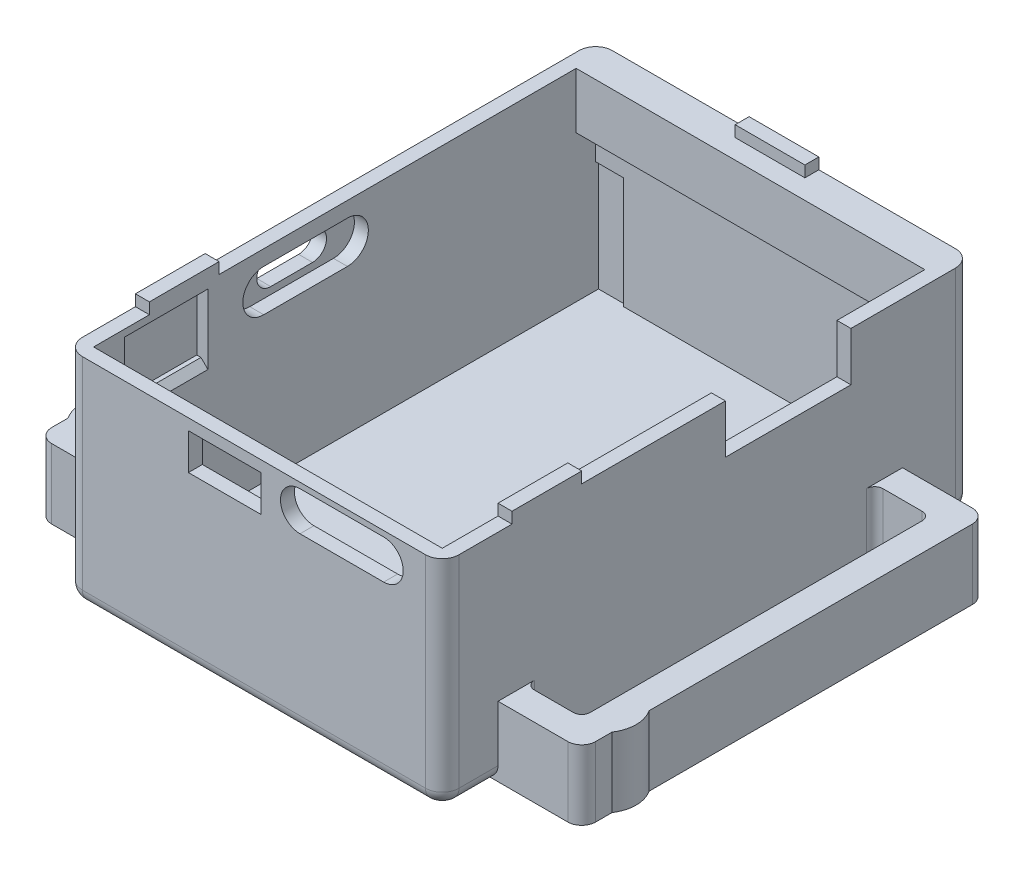
SolidWorks part; units mm, degrees
ref_plane "前视基准面" through (0, 0, 0) normal (0, 0, 1) x (1, 0, 0)
ref_plane "上视基准面" through (0, 0, 0) normal (0, 1, 0) x (1, 0, 0)
ref_plane "右视基准面" through (0, 0, 0) normal (1, 0, 0) x (0, 0, -1)
other "Configuration Table"
sketch "草图1" plane through (0, 0, 0) normal (0, 1, 0) x (1, 0, 0)
  line L1 (-12.5, -18) -> (12.5, -18) construction
  line L2 (-12.5, -18) -> (-12.5, 18) construction
  line L3 (-12.5, 18) -> (12.5, 18) construction
  line L4 (12.5, -18) -> (12.5, 18) construction
  line L5 (-12.5, -18) -> (12.5, 18) construction
  line L6 (-12.5, 18) -> (12.5, -18) construction
  line L7 (-13.5, -19) -> (13.5, -19)
  line L8 (-13.5, -19) -> (-13.5, 19)
  line L9 (-13.5, 19) -> (13.5, 19)
  line L10 (13.5, -19) -> (13.5, 19)
  line L11 (-13.5, -19) -> (13.5, 19) construction
  line L12 (-13.5, 19) -> (13.5, -19) construction
  point P0 (0, 0)
  point P6 (0, 0)
  dimension "D1" = 25
  dimension "D2" = 36
  dimension "D3" = 1
  dimension "D4" = 1
extrude "凸台-拉伸1" add sketch "草图1" along normal blind 1
sketch "草图3" plane through (0, 1, 0) normal (0, 1, 0) x (1, 0, 0)
  line L1 (-13.5, -19) -> (13.5, -19)
  line L2 (-13.5, -19) -> (-13.5, 19)
  line L3 (-13.5, 19) -> (13.5, 19)
  line L4 (13.5, -19) -> (13.5, 19)
  line L5 (-13.5, -19) -> (13.5, 19) construction
  line L6 (-13.5, 19) -> (13.5, -19) construction
  line L7 (-12.5, -18) -> (12.5, -18)
  line L8 (-12.5, -18) -> (-12.5, 18)
  line L9 (-12.5, 18) -> (12.5, 18)
  line L10 (12.5, -18) -> (12.5, 18)
  line L11 (-12.5, -18) -> (12.5, 18) construction
  line L12 (-12.5, 18) -> (12.5, -18) construction
  point P0 (0, 0)
  point P7 (0, 0)
  dimension "D1" = 1
  dimension "D2" = 1
  dimension "D3" = 38
  dimension "D4" = 27
extrude "凸台-拉伸2" add sketch "草图3" along normal blind 14.5
fillet "圆角1" radius 1.2 4 edges at (13.5, 7.75, -19) (-13.5, 7.75, -19) (-13.5, 7.75, 19) (13.5, 7.75, 19)
sketch "草图4" plane through (0, 0, 0) normal (0, -1, 0) x (1, 0, 0)
  line L0 (13.5, 17.8) -> (13.5, -17.8) construction
  line L1 (13.5, 15) -> (19.5, 15)
  line L2 (13.5, 15) -> (13.5, 13)
  line L3 (13.5, -14) -> (19.5, -14)
  line L4 (19.5, 15) -> (19.5, -14)
  line L5 (0, 19) -> (0, -19) construction
  line L6 (13.5, 13) -> (17.5, 13)
  line L8 (13.5, -12) -> (17.5, -12)
  line L9 (17.5, 13) -> (17.5, -12)
  line L10 (-12.3, 19) -> (12.3, 19) construction
  line L11 (12.3, -19) -> (-12.3, -19) construction
  line L12 (-17.5, 13) -> (-17.5, -12)
  line L13 (-13.5, -12) -> (-17.5, -12)
  line L15 (-13.5, 13) -> (-17.5, 13)
  line L16 (-19.5, 15) -> (-19.5, -14)
  line L17 (-13.5, -14) -> (-19.5, -14)
  line L18 (-13.5, 15) -> (-13.5, 13)
  line L19 (-13.5, 15) -> (-19.5, 15)
  line L20 (-13.5, -12) -> (-13.5, -14)
  line L21 (13.5, -12) -> (13.5, -14)
  dimension "D1" = 6
  dimension "D2" = 29
  dimension "D3" = 2
  dimension "D4" = 2
  dimension "D5" = 2
  dimension "D6" = 4
extrude "凸台-拉伸3" add sketch "草图4" against normal blind 5
fillet "圆角3" radius 1 4 edges at (-19.5, 2.5, 15) (-19.5, 2.5, -14) (19.5, 2.5, 15) (19.5, 2.5, -14)
fillet "圆角4" radius 0.6 8 edges at (-17.5, 2.5, 13) (-17.5, 2.5, -12) (-13.5, 2.5, 13) (-13.5, 2.5, -12) (17.5, 2.5, 13) (13.5, 2.5, 13) (13.5, 2.5, -12) (17.5, 2.5, -12)
fillet "圆角6" radius 1 10 edges at (13.5, 0, -15.9) (13.1485, 0, -18.6485) (-13.5, 0, -15.9) (-13.1485, 0, -18.6485) (-13.5, 0, 16.4) (-13.1485, 0, 18.6485) (13.5, 0, 16.4) (13.1485, 0, 18.6485) (0, 0, -19) (0, 0, 19)
sketch "草图5" plane through (0, 0, 19) normal (0, 0, 1) x (1, 0, 0)
  line L0 (3.3, 13.7) -> (9.3, 13.7) construction
  line L1 (3.3, 15.1) -> (9.3, 15.1)
  line L2 (3.3, 12.3) -> (9.3, 12.3)
  line L3 (12.3, 1) -> (12.3, 15.5) construction
  line L4 (-12.3, 15.5) -> (12.3, 15.5) construction
  arc A0 (3.3, 15.1) -> (3.3, 12.3) centre (3.3, 13.7) ccw
  arc A1 (9.3, 12.3) -> (9.3, 15.1) centre (9.3, 13.7) ccw
  point P2 (6.3, 13.7)
  dimension "D2" = 6
  dimension "D3" = 1.4
  dimension "D1" = 6
  dimension "D4" = 0.4
extrude "切除-拉伸1" cut sketch "草图5" against normal up to next
sketch "草图6" plane through (13.5, 0, 0) normal (1, 0, 0) x (0, 0, -1)
  line L0 (-17.8, 15.5) -> (17.8, 15.5) construction
  line L1 (1.3, 15.5) -> (10.3, 15.5)
  line L2 (1.3, 15.5) -> (1.3, 12)
  line L3 (1.3, 12) -> (10.3, 12)
  line L4 (10.3, 15.5) -> (10.3, 12)
  line L6 (-19, 1) -> (-19, 15.5) construction
  dimension "D1" = 3.5
  dimension "D2" = 9
  dimension "D3" = 20.3
extrude "切除-拉伸2" cut sketch "草图6" against normal up to next
sketch "草图7" plane through (0, 0, 0) normal (0, -1, 0) x (1, 0, 0)
  line L0 (17.5, 12.4) -> (17.5, -11.4) construction
  line L1 (18.5, 15) -> (12.5, 15) construction
  line L2 (0, 18) -> (0, -18) construction
  line L3 (12.3, 18) -> (-12.3, 18) construction
  line L4 (-12.3, -18) -> (12.3, -18) construction
  line L5 (19.5, 12.8266) -> (19.5, 10.1734)
  line L6 (19.5, -13) -> (19.5, 14) construction
  line L7 (-19.5, 12.8266) -> (-19.5, 10.1734)
  arc A0 (19.5, 10.1734) -> (19.5, 12.8266) centre (17.5, 11.5) ccw
  arc A1 (-19.5, 10.1734) -> (-19.5, 12.8266) centre (-17.5, 11.5) cw
  dimension "D2" = 4.8
  dimension "D1" = 3.5
extrude "凸台-拉伸4" add sketch "草图7" against normal blind 5
sketch "草图8" plane through (0, 0, 19) normal (0, 0, 1) x (1, 0, 0)
  line L0 (-12.3, 15.5) -> (12.3, 15.5) construction
  line L1 (-4.7, 14.7) -> (0.5, 14.7)
  line L2 (-4.7, 14.7) -> (-4.7, 12.1)
  line L3 (-4.7, 12.1) -> (0.5, 12.1)
  line L4 (0.5, 14.7) -> (0.5, 12.1)
  line L5 (-13.5, 1) -> (-13.5, 15.5) construction
  dimension "D1" = 0.8
  dimension "D2" = 8.8
  dimension "D3" = 5.2
  dimension "D4" = 2.6
extrude "切除-拉伸3" cut sketch "草图8" against normal up to next
sketch "草图13" plane through (-12.5, 0, 0) normal (1, 0, 0) x (0, 0, -1)
  line L0 (-17.8, 15.5) -> (-17.8, 1) construction
  line L1 (-15.8, 14.5) -> (-9.8, 14.5)
  line L2 (-15.8, 14.5) -> (-15.8, 10.5)
  line L3 (-15.8, 10.5) -> (-9.8, 10.5)
  line L4 (-9.8, 14.5) -> (-9.8, 10.5)
  line L5 (18, 15.5) -> (-18, 15.5) construction
  dimension "D1" = 2
  dimension "D2" = 6
  dimension "D3" = 4
  dimension "D4" = 1
extrude "切除-拉伸6" cut sketch "草图13" against normal blind 0.8
sketch "草图15" plane through (0, 0, -18) normal (0, 0, 1) x (1, 0, 0)
  line L0 (12.5, 15.5) -> (12.5, 1) construction
  line L1 (-12.5, 15.5) -> (12.5, 15.5)
  line L2 (-12.5, 15.5) -> (-12.5, 10.5)
  line L3 (-12.5, 10.5) -> (12.5, 10.5)
  line L4 (12.5, 15.5) -> (12.5, 10.5)
  dimension "D1" = 5
extrude "凸台-拉伸5" add sketch "草图15" along normal blind 1.4
chamfer "倒角3" distance 1 angle 45 1 edges at (0, 10.5, -16.6)
sketch "草图16" plane through (0, 1, 0) normal (0, 1, 0) x (1, 0, 0)
  line L0 (12.5, -18) -> (12.5, 18) construction
  line L1 (-12.5, 18) -> (-10.5, 18)
  line L2 (-12.5, 18) -> (-12.5, 18.2)
  line L3 (-12.5, 18.2) -> (-10.5, 18.2)
  line L4 (-10.5, 18) -> (-10.5, 18.2)
  line L5 (12.1, 18) -> (10.1, 18)
  line L6 (12.1, 18) -> (12.1, 18.2)
  line L7 (12.1, 18.2) -> (10.1, 18.2)
  line L8 (10.1, 18) -> (10.1, 18.2)
  dimension "D1" = 0.2
  dimension "D2" = 0.2
  dimension "D3" = 2
  dimension "D4" = 2
  dimension "D5" = 0.4
extrude "切除-拉伸7" cut sketch "草图16" along normal blind 8
sketch "草图18" plane through (0, 15.5, 0) normal (0, 1, 0) x (1, 0, 0)
  line L0 (12.3, 19) -> (-12.3, 19) construction
  line L1 (-2.5, 19) -> (2.5, 19)
  line L2 (-2.5, 19) -> (-2.5, 18)
  line L3 (-2.5, 18) -> (2.5, 18)
  line L4 (2.5, 19) -> (2.5, 18)
  line L5 (-12.5, 16.6) -> (-12.5, -18) construction
  line L6 (-13.5, 17.8) -> (-13.5, -17.8) construction
  line L8 (-13.5, -9) -> (-12.5, -9)
  line L9 (-13.5, -9) -> (-13.5, -14)
  line L10 (-13.5, -14) -> (-12.5, -14)
  line L11 (-12.5, -9) -> (-12.5, -14)
  line L12 (12.5, -18) -> (12.5, 1.3) construction
  line L13 (12.5, -9) -> (13.5, -9)
  line L14 (12.5, -9) -> (12.5, -14)
  line L15 (12.5, -14) -> (13.5, -14)
  line L16 (13.5, -9) -> (13.5, -14)
  line L17 (13.5, -17.8) -> (13.5, 1.3) construction
  line L18 (-12.3, -19) -> (12.3, -19) construction
  point P6 (0, 19)
  point P7 (0, 19)
  dimension "D1" = 5
  dimension "D2" = 1
  dimension "D3" = 5
  dimension "D4" = 5
  dimension "D5" = 5
  dimension "D6" = 5
extrude "凸台-拉伸6" add sketch "草图18" along normal blind 0.8
sketch "草图19" plane through (-13.5, 0, 0) normal (-1, 0, 0) x (0, 0, 1)
  line L0 (-17.8, 15.5) -> (9, 15.5) construction
  line L6 (-0.2, 12.9) -> (5.8, 12.9) construction
  line L7 (-0.2, 14.9) -> (5.8, 14.9)
  line L8 (-0.2, 10.9) -> (5.8, 10.9)
  line L9 (19, 15.5) -> (19, 1) construction
  arc A0 (-0.2, 14.9) -> (-0.2, 10.9) centre (-0.2, 12.9) ccw
  arc A1 (5.8, 10.9) -> (5.8, 14.9) centre (5.8, 12.9) ccw
  point P10 (2.8, 12.9)
  dimension "D4" = 2
  dimension "D1" = 19.2
  dimension "D2" = 0.6
  dimension "D3" = 6
extrude "凸台-拉伸9" add sketch "草图19" along normal blind 1
sketch "草图20" plane through (-14.5, 0, 0) normal (-1, 0, 0) x (0, 0, 1)
  line L0 (2.3, 12.9) -> (5.3, 12.9) construction
  line L5 (1.3, 12.9) -> (4.3, 12.9) construction
  line L6 (1.3, 13.9) -> (4.3, 13.9)
  line L9 (5.8, 14.9) -> (-0.2, 14.9) construction
  line L12 (1.3, 11.9) -> (4.3, 11.9)
  line L13 (2.8, 14.9) -> (2.8, 10.9) construction
  line L14 (-0.2, 10.9) -> (5.8, 10.9) construction
  arc A0 (1.3, 13.9) -> (1.3, 11.9) centre (1.3, 12.9) ccw
  arc A1 (4.3, 11.9) -> (4.3, 13.9) centre (4.3, 12.9) ccw
  arc A2 (5.8, 10.9) -> (5.8, 14.9) centre (5.8, 12.9) ccw construction
  point P2 (2.8, 12.9)
  point P14 (2.8, 12.9)
  point P20 (7.8, 12.9)
  dimension "D1" = 1
  dimension "D3" = 3.5
  dimension "D2" = 3
  dimension "D4" = 3
  dimension "D5" = 1
extrude "切除-拉伸8" cut sketch "草图20" against normal up to next
sketch "草图21" plane through (-12.5, 0, 0) normal (1, 0, 0) x (0, 0, -1)
  line L2 (-5.8, 12.9) -> (0.2, 12.9) construction
  line L3 (-5.8, 14.4) -> (0.2, 14.4)
  line L4 (-5.8, 11.4) -> (0.2, 11.4)
  arc A0 (-5.8, 14.4) -> (-5.8, 11.4) centre (-5.8, 12.9) ccw
  arc A1 (0.2, 11.4) -> (0.2, 14.4) centre (0.2, 12.9) ccw
  arc A4 (0.2, 10.9) -> (0.2, 14.9) centre (0.2, 12.9) ccw construction
  arc A5 (-5.8, 14.9) -> (-5.8, 10.9) centre (-5.8, 12.9) ccw construction
  point P10 (-2.8, 12.9)
  dimension "D1" = 1.5
  dimension "D2" = 6
extrude "切除-拉伸9" cut sketch "草图21" against normal blind 1
chamfer "倒角4" distance 0.5 angle 45 4 edges at (-14.5, 12.9, -2.2) (-14.5, 10.9, 2.8) (-14.5, 12.9, 7.8) (-14.5, 14.9, 2.8)
sketch "草图22" plane through (-13.5, 0, 0) normal (-1, 0, 0) x (0, 0, 1)
  line L0 (14, 15.5) -> (17.8, 15.5) construction
  line L1 (8.8, 15.5) -> (16.8, 15.5)
  line L2 (8.8, 15.5) -> (8.8, 9.5)
  line L3 (8.8, 9.5) -> (16.8, 9.5)
  line L4 (16.8, 15.5) -> (16.8, 9.5)
  line L5 (17.8, 1) -> (17.8, 15.5) construction
  dimension "D1" = 8
  dimension "D2" = 6
  dimension "D3" = 1
extrude "凸台-拉伸10" add sketch "草图22" along normal blind 0.8
chamfer "倒角6" distance 0.8 angle 45 4 edges at (-14.3, 12.5, 16.8) (-14.3, 9.5, 12.8) (-14.3, 15.5, 12.8) (-14.3, 12.5, 8.8)
chamfer "倒角7" distance 0.5 angle 45 2 edges at (-12.5, 10.5, 12.8) (-12.5, 14.5, 12.8)
